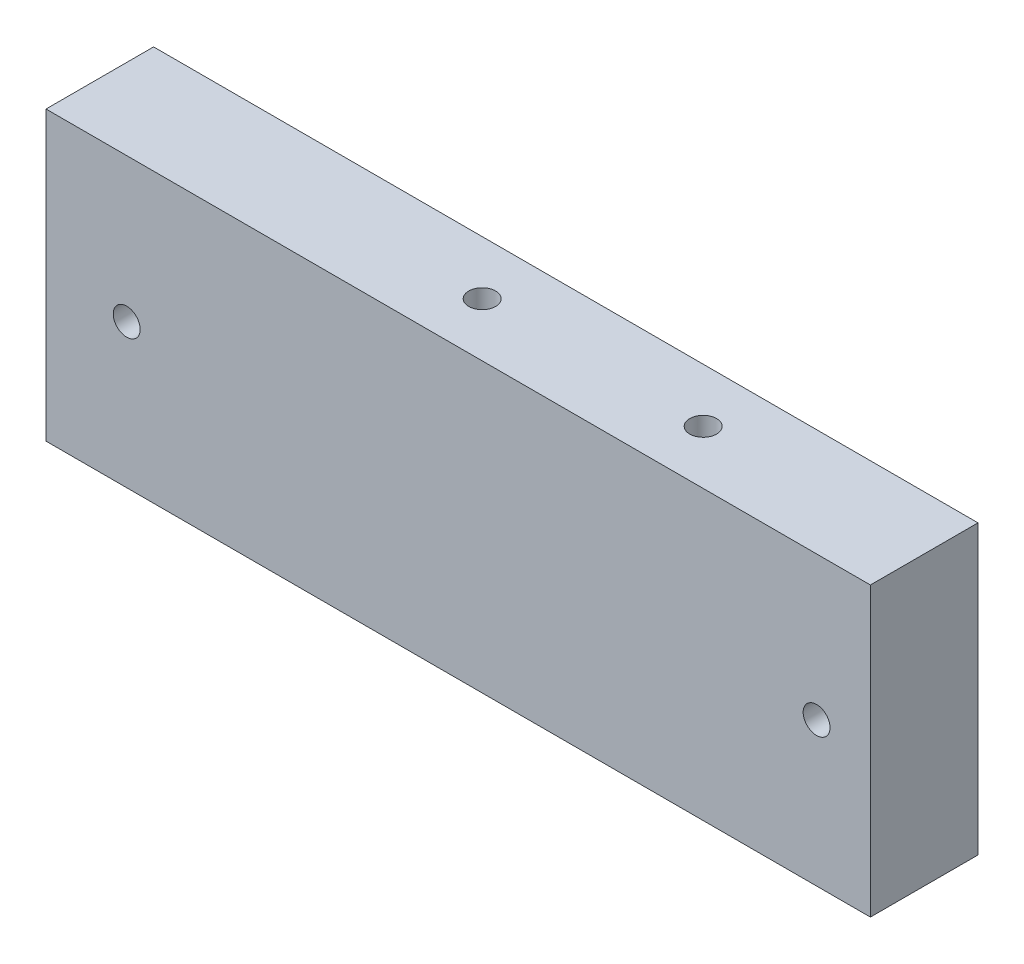
SolidWorks part; units mm, degrees
material "Beech"
ref_plane "Front Plane" through (0, 0, 0) normal (0, 0, 1) x (1, 0, 0)
ref_plane "Top Plane" through (0, 0, 0) normal (0, 1, 0) x (1, 0, 0)
ref_plane "Right Plane" through (0, 0, 0) normal (1, 0, 0) x (0, 0, -1)
sketch "Sketch1" plane through (0, 0, 0) normal (0, 0, 1) x (1, 0, 0)
  line L0 (-244.0045, -53) -> (-244.0045, -19) construction
  line L1 (-341.3045, -19.05) -> (-244.0045, -19.05)
  line L2 (-341.3045, -19.05) -> (-341.3045, -53)
  line L3 (-341.3045, -53) -> (-244.0045, -53)
  line L4 (-244.0045, -19.05) -> (-244.0045, -53)
  dimension "D2" = 33.95
extrude "Boss-Extrude1" add sketch "Sketch1" against normal blind 12.7
hole_wizard "Hole1" positions "Sketch2" profile "Sketch3" legacy
sketch "Sketch2" plane through (-124.0045, 0, -10.4243) normal (0, 1, 0) x (-1, 0, 0)
  line L21 (0, 109.0243) -> (0, 155.0243) construction
  point P37 (126.35, 161.3743)
  point P42 (146.0833, 4.0743)
  point P44 (172.1667, 4.0743)
  point P63 (126.35, 34.5243)
  point P65 (126.35, 130.9243)
  point P76 (-172.1667, 4.0743)
  point P77 (-146.0833, 4.0743)
  point P78 (-126.35, 34.5243)
  point P79 (-126.35, 130.9243)
  point P80 (-126.35, 161.3743)
sketch "Sketch3" plane through (-250.3545, 0, 150.95) normal (1, 0, 0) x (0, 0, 1)
  line L0 (0, 0) -> (0, 32.7039)
  line L1 (0, 32.7039) -> (1.5875, 31.75)
  line L2 (1.5875, 31.75) -> (1.5875, 4.0177)
  line L3 (1.5875, 4.0177) -> (5.08, 0)
  line L4 (5.08, 0) -> (0, 0)
  line L5 (0, -14.3089) -> (0, 102.4216) construction
  line L6 (0, 32.7039) -> (-1.5875, 31.75) construction
  line L7 (-1.5875, 4.0177) -> (-5.08, 0) construction
  dimension "Diameter" = 3.175
  dimension "Depth" = 31.75
  dimension "C-Sink Diameter" = 10.16
  dimension "C-Sink Angle" = 82
  dimension "Drill Angle" = 118
hole_wizard "Hole2" positions "Sketch4" profile "Sketch5" legacy
sketch "Sketch4" plane through (-124.0045, -72.05, -10.4243) normal (0, -1, 0) x (1, 0, 0)
  line L21 (0, 109.0243) -> (0, 155.0243) construction
  point P37 (126.35, 161.3743)
  point P42 (146.0833, 4.0743)
  point P44 (172.1667, 4.0743)
  point P63 (126.35, 34.5243)
  point P65 (126.35, 130.9243)
  point P76 (-172.1667, 4.0743)
  point P77 (-146.0833, 4.0743)
  point P78 (-126.35, 34.5243)
  point P79 (-126.35, 130.9243)
  point P80 (-126.35, 161.3743)
sketch "Sketch5" plane through (2.3455, -72.05, 150.95) normal (1, 0, 0) x (0, 0, -1)
  line L0 (0, 0) -> (0, 32.7039)
  line L1 (0, 32.7039) -> (1.5875, 31.75)
  line L2 (1.5875, 31.75) -> (1.5875, 4.0177)
  line L3 (1.5875, 4.0177) -> (5.08, 0)
  line L4 (5.08, 0) -> (0, 0)
  line L5 (0, -14.3089) -> (0, 102.4216) construction
  line L6 (0, 32.7039) -> (-1.5875, 31.75) construction
  line L7 (-1.5875, 4.0177) -> (-5.08, 0) construction
  dimension "Diameter" = 3.175
  dimension "Depth" = 31.75
  dimension "C-Sink Diameter" = 10.16
  dimension "C-Sink Angle" = 82
  dimension "Drill Angle" = 118
hole_wizard "Hole5" positions "Sketch8" profile "Sketch9" legacy
sketch "Sketch8" plane through (-124.0045, -208.2867, -12.7) normal (0, 0, -1) x (-1, 0, 0)
  line L0 (120, 172.2617) -> (217.3, 172.2617) construction
  point P8 (126.35, 172.2617)
  point P10 (207.775, 172.2617)
sketch "Sketch9" plane through (-331.7795, -36.025, -12.7) normal (1, 0, 0) x (0, 1, 0)
  line L0 (0, 0) -> (0, 32.7039)
  line L1 (0, 32.7039) -> (1.5875, 31.75)
  line L2 (1.5875, 31.75) -> (1.5875, 4.0177)
  line L3 (1.5875, 4.0177) -> (5.08, 0)
  line L4 (5.08, 0) -> (0, 0)
  line L5 (0, -14.3089) -> (0, 102.4216) construction
  line L6 (0, 32.7039) -> (-1.5875, 31.75) construction
  line L7 (-1.5875, 4.0177) -> (-5.08, 0) construction
  dimension "Diameter" = 3.175
  dimension "Depth" = 31.75
  dimension "C-Sink Diameter" = 10.16
  dimension "C-Sink Angle" = 82
  dimension "Drill Angle" = 118
hole_wizard "Hole6" positions "Sketch10" profile "Sketch11" legacy
sketch "Sketch10" plane through (-124.0045, -6.35, -10.4243) normal (0, 1, 0) x (-1, 0, 0)
  line L12 (0, 0) -> (0, 155.0243) construction
  point P0 (-207.775, 333.0214)
  point P3 (-207.775, 225.489)
  point P6 (-207.775, 137.4243)
  point P9 (-172.1667, 4.0743)
  point P12 (-146.0833, 4.0743)
  point P15 (-94.6, 161.3743)
  point P21 (94.6, 161.3743)
  point P24 (146.0833, 4.0743)
  point P27 (172.1667, 4.0743)
  point P30 (207.775, 137.4243)
  point P33 (207.775, 225.489)
  point P36 (207.775, 333.0214)
  point P39 (166.7958, 301.9704)
  point P42 (40.9792, 301.9704)
  point P45 (-40.9792, 301.9704)
  point P48 (-166.7958, 301.9704)
  point P51 (0, 193.1243)
  point P54 (0, 301.9704)
  point P57 (0, 412.3664)
  point P80 (-126.35, 106.8243)
  point P82 (-126.35, 58.6243)
  point P96 (126.35, 58.6243)
  point P97 (126.35, 106.8243)
  point P99 (0, 0)
sketch "Sketch11" plane through (83.7705, -6.35, 322.5971) normal (1, 0, 0) x (0, 0, 1)
  line L0 (0, 0) -> (0, 32.7039)
  line L1 (0, 32.7039) -> (1.5875, 31.75)
  line L2 (1.5875, 31.75) -> (1.5875, 4.0177)
  line L3 (1.5875, 4.0177) -> (5.08, 0)
  line L4 (5.08, 0) -> (0, 0)
  line L5 (0, -14.3089) -> (0, 102.4216) construction
  line L6 (0, 32.7039) -> (-1.5875, 31.75) construction
  line L7 (-1.5875, 4.0177) -> (-5.08, 0) construction
  dimension "Diameter" = 3.175
  dimension "Depth" = 31.75
  dimension "C-Sink Diameter" = 10.16
  dimension "C-Sink Angle" = 82
  dimension "Drill Angle" = 118
